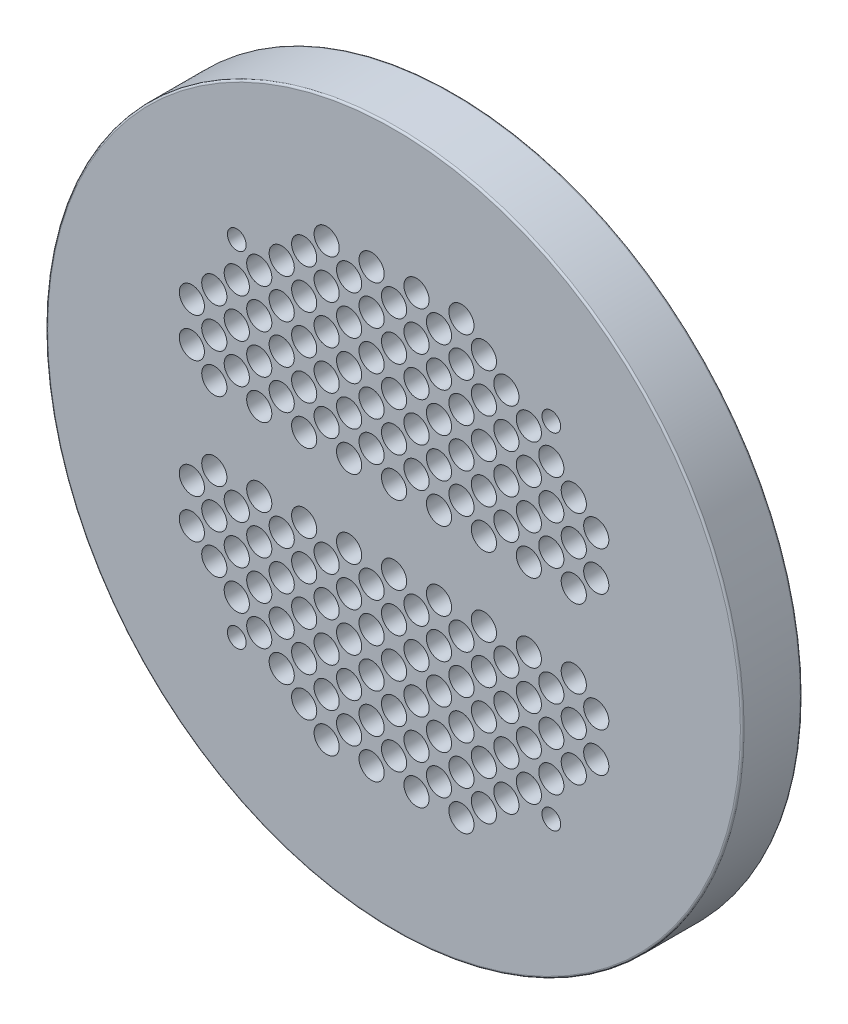
SolidWorks part; units mm, degrees
material "ASTM A105"
ref_plane "Front Plane" through (0, 0, 0) normal (0, 0, 1) x (1, 0, 0)
ref_plane "Top Plane" through (0, 0, 0) normal (0, 1, 0) x (1, 0, 0)
ref_plane "Right Plane" through (0, 0, 0) normal (1, 0, 0) x (0, 0, -1)
ref_axis "Axis1" through (0, 0, -1.27) along (0, 0, 1)
ref_plane "Hub End Plane" through (0, 0, 88.9) normal (0, 0, 1) x (1, 0, 0)
sketch "Sketch1" plane through (0, 0, 0) normal (0, 0, 1) x (1, 0, 0)
  line L0 (0, 314.325) -> (0, 0) construction
  line L1 (41.0276, 311.6359) -> (0, 0) construction
  circle A1 centre (0, 0) radius 295.275
  circle A2 centre (0, 0) radius 314.325 construction
  circle A3 centre (41.0276, 311.6359) radius 17.4625 construction
  dimension "FlangeOD" = 590.55
  dimension "BoltHoleDia" = 34.925
  dimension "BoltCircle" = 628.65
  dimension "HoleOffsetAngle" = 7.5
extrude "Boss-Extrude1" add sketch "Sketch1" along normal blind 50.8
sketch "Sketch7" plane through (0, 0, 0) normal (0, 0, 1) x (1, 0, 0)
  circle A0 centre (0, 0) radius 230.886
  dimension "ID" = 461.772
fillet "Fillet2" radius 1.5875 2 edges at (295.275, 0, 50.8) (295.275, 0, 0)
ref_plane "lug mating plane" through (0, 0, 25.4) normal (0, 0, 1) x (1, 0, 0)
sketch "Sketch11" plane through (0, 0, 0) normal (0, 0, 1) x (1, 0, 0)
  line L0 (-313.3441, 0) -> (312.1404, 0) construction
  line L1 (0, 318.8395) -> (0, -323.6955) construction
  circle A3 centre (0, 33.02) radius 10.668
  circle A15 centre (38.1, 33.02) radius 10.668
  circle A16 centre (76.2, 33.02) radius 10.668
  circle A17 centre (114.3, 33.02) radius 10.668
  circle A18 centre (152.4, 33.02) radius 10.668
  circle A20 centre (-38.1, 33.02) radius 10.668
  circle A21 centre (-76.2, 33.02) radius 10.668
  circle A22 centre (-114.3, 33.02) radius 10.668
  circle A23 centre (-152.4, 33.02) radius 10.668
  circle A88 centre (0, 66.3575) radius 10.668
  circle A89 centre (38.1, 66.3575) radius 10.668
  circle A90 centre (76.2, 66.3575) radius 10.668
  circle A91 centre (114.3, 66.3575) radius 10.668
  circle A93 centre (152.4, 66.3575) radius 10.668
  circle A95 centre (-38.1, 66.3575) radius 10.668
  circle A98 centre (-76.2, 66.3575) radius 10.668
  circle A146 centre (-114.3, 66.3575) radius 10.668
  circle A150 centre (-152.4, 66.3575) radius 10.668
  circle A152 centre (0, 99.695) radius 10.668
  circle A153 centre (38.1, 99.695) radius 10.668
  circle A154 centre (76.2, 99.695) radius 10.668
  circle A156 centre (114.3, 99.695) radius 10.668
  circle A158 centre (152.4, 99.695) radius 10.668
  circle A161 centre (-38.1, 99.695) radius 10.668
  circle A163 centre (-76.2, 99.695) radius 10.668
  circle A164 centre (-114.3, 99.695) radius 10.668
  circle A166 centre (-133.35, 146.05) radius 7.9375
  circle A172 centre (-152.4, 99.695) radius 10.668
  circle A174 centre (0, 133.0325) radius 10.668
  circle A175 centre (38.1, 133.0325) radius 10.668
  circle A176 centre (76.2, 133.0325) radius 10.668
  circle A177 centre (114.3, 133.0325) radius 10.668
  circle A180 centre (-38.1, 133.0325) radius 10.668
  circle A181 centre (-76.2, 133.0325) radius 10.668
  circle A182 centre (-114.3, 133.0325) radius 10.668
  circle A185 centre (0, 166.37) radius 10.668
  circle A186 centre (38.1, 166.37) radius 10.668
  circle A187 centre (76.2, 166.37) radius 10.668
  circle A191 centre (-38.1, 166.37) radius 10.668
  circle A192 centre (-76.2, 166.37) radius 10.668
  circle A207 centre (19.05, 49.8475) radius 10.668
  circle A208 centre (-19.05, 49.8475) radius 10.668
  circle A209 centre (-57.15, 49.8475) radius 10.668
  circle A210 centre (-95.25, 49.8475) radius 10.668
  circle A211 centre (-133.35, 49.8475) radius 10.668
  circle A212 centre (-171.45, 49.8475) radius 10.668
  circle A213 centre (57.15, 49.8475) radius 10.668
  circle A214 centre (95.25, 49.8475) radius 10.668
  circle A215 centre (133.35, 49.8475) radius 10.668
  circle A216 centre (171.45, 49.8475) radius 10.668
  circle A217 centre (19.05, 83.185) radius 10.668
  circle A218 centre (-19.05, 83.185) radius 10.668
  circle A219 centre (-57.15, 83.185) radius 10.668
  circle A220 centre (-95.25, 83.185) radius 10.668
  circle A221 centre (-133.35, 83.185) radius 10.668
  circle A222 centre (-171.45, 83.185) radius 10.668
  circle A223 centre (57.15, 83.185) radius 10.668
  circle A224 centre (95.25, 83.185) radius 10.668
  circle A225 centre (133.35, 83.185) radius 10.668
  circle A226 centre (171.45, 83.185) radius 10.668
  circle A227 centre (19.05, 116.5225) radius 10.668
  circle A228 centre (-19.05, 116.5225) radius 10.668
  circle A229 centre (-57.15, 116.5225) radius 10.668
  circle A230 centre (-95.25, 116.5225) radius 10.668
  circle A231 centre (-133.35, 116.5225) radius 10.668
  circle A233 centre (57.15, 116.5225) radius 10.668
  circle A234 centre (95.25, 116.5225) radius 10.668
  circle A235 centre (133.35, 116.5225) radius 10.668
  circle A237 centre (19.05, 149.86) radius 10.668
  circle A238 centre (-19.05, 149.86) radius 10.668
  circle A239 centre (-57.15, 149.86) radius 10.668
  circle A240 centre (-95.25, 149.86) radius 10.668
  circle A243 centre (57.15, 149.86) radius 10.668
  circle A244 centre (95.25, 149.86) radius 10.668
  circle A247 centre (19.05, 183.1975) radius 10.668
  circle A248 centre (-19.05, 183.1975) radius 10.668
  circle A249 centre (-57.15, 183.1975) radius 10.668
  circle A253 centre (57.15, 183.1975) radius 10.668
  circle A257 centre (-133.35, -146.05) radius 7.9375
  circle A258 centre (133.35, -146.05) radius 7.9375
  circle A262 centre (152.4, 199.7075) radius 10.668 [skipped]
  circle A263 centre (152.4, 166.37) radius 10.668 [skipped]
  circle A265 centre (114.3, 199.7075) radius 10.668 [skipped]
  circle A267 centre (-152.4, 199.7075) radius 10.668 [skipped]
  circle A268 centre (-114.3, 199.7075) radius 10.668 [skipped]
  circle A271 centre (-152.4, 166.37) radius 10.668 [skipped]
  circle A275 centre (152.4, 133.0325) radius 10.668 [skipped]
  circle A278 centre (114.3, 166.37) radius 10.668 [skipped]
  circle A280 centre (76.2, 199.7075) radius 10.668 [skipped]
  circle A281 centre (-114.3, 166.37) radius 10.668 [skipped]
  circle A283 centre (-76.2, 199.7075) radius 10.668 [skipped]
  circle A284 centre (-152.4, 133.0325) radius 10.668 [skipped]
  circle A288 centre (-190.5, 33.02) radius 10.668 [skipped]
  circle A290 centre (190.5, 33.02) radius 10.668 [skipped]
  circle A291 centre (38.1, 199.7075) radius 10.668 [skipped]
  circle A292 centre (0, 199.7075) radius 10.668 [skipped]
  circle A293 centre (-38.1, 199.7075) radius 10.668 [skipped]
  circle A294 centre (133.35, 146.05) radius 7.9375
  circle A299 centre (57.15, -183.1975) radius 10.668
  circle A300 centre (-57.15, -183.1975) radius 10.668
  circle A301 centre (-19.05, -183.1975) radius 10.668
  circle A302 centre (19.05, -183.1975) radius 10.668
  circle A303 centre (95.25, -149.86) radius 10.668
  circle A304 centre (57.15, -149.86) radius 10.668
  circle A305 centre (-95.25, -149.86) radius 10.668
  circle A306 centre (-57.15, -149.86) radius 10.668
  circle A307 centre (-19.05, -149.86) radius 10.668
  circle A308 centre (19.05, -149.86) radius 10.668
  circle A309 centre (133.35, -116.5225) radius 10.668
  circle A310 centre (95.25, -116.5225) radius 10.668
  circle A311 centre (57.15, -116.5225) radius 10.668
  circle A312 centre (-133.35, -116.5225) radius 10.668
  circle A313 centre (-95.25, -116.5225) radius 10.668
  circle A314 centre (-57.15, -116.5225) radius 10.668
  circle A315 centre (-19.05, -116.5225) radius 10.668
  circle A316 centre (19.05, -116.5225) radius 10.668
  circle A317 centre (171.45, -83.185) radius 10.668
  circle A318 centre (133.35, -83.185) radius 10.668
  circle A319 centre (95.25, -83.185) radius 10.668
  circle A320 centre (57.15, -83.185) radius 10.668
  circle A321 centre (-171.45, -83.185) radius 10.668
  circle A322 centre (-133.35, -83.185) radius 10.668
  circle A323 centre (-95.25, -83.185) radius 10.668
  circle A324 centre (-57.15, -83.185) radius 10.668
  circle A325 centre (-19.05, -83.185) radius 10.668
  circle A326 centre (19.05, -83.185) radius 10.668
  circle A327 centre (171.45, -49.8475) radius 10.668
  circle A328 centre (133.35, -49.8475) radius 10.668
  circle A329 centre (95.25, -49.8475) radius 10.668
  circle A330 centre (57.15, -49.8475) radius 10.668
  circle A331 centre (-171.45, -49.8475) radius 10.668
  circle A332 centre (-133.35, -49.8475) radius 10.668
  circle A333 centre (-95.25, -49.8475) radius 10.668
  circle A334 centre (-57.15, -49.8475) radius 10.668
  circle A335 centre (-19.05, -49.8475) radius 10.668
  circle A336 centre (19.05, -49.8475) radius 10.668
  circle A337 centre (-76.2, -166.37) radius 10.668
  circle A338 centre (-38.1, -166.37) radius 10.668
  circle A339 centre (76.2, -166.37) radius 10.668
  circle A340 centre (38.1, -166.37) radius 10.668
  circle A341 centre (0, -166.37) radius 10.668
  circle A342 centre (-114.3, -133.0325) radius 10.668
  circle A343 centre (-76.2, -133.0325) radius 10.668
  circle A344 centre (-38.1, -133.0325) radius 10.668
  circle A345 centre (114.3, -133.0325) radius 10.668
  circle A346 centre (76.2, -133.0325) radius 10.668
  circle A347 centre (38.1, -133.0325) radius 10.668
  circle A348 centre (0, -133.0325) radius 10.668
  circle A349 centre (-152.4, -99.695) radius 10.668
  circle A350 centre (-114.3, -99.695) radius 10.668
  circle A351 centre (-76.2, -99.695) radius 10.668
  circle A352 centre (-38.1, -99.695) radius 10.668
  circle A353 centre (152.4, -99.695) radius 10.668
  circle A354 centre (114.3, -99.695) radius 10.668
  circle A355 centre (76.2, -99.695) radius 10.668
  circle A356 centre (38.1, -99.695) radius 10.668
  circle A357 centre (0, -99.695) radius 10.668
  circle A358 centre (-152.4, -66.3575) radius 10.668
  circle A359 centre (-114.3, -66.3575) radius 10.668
  circle A360 centre (-76.2, -66.3575) radius 10.668
  circle A361 centre (-38.1, -66.3575) radius 10.668
  circle A362 centre (152.4, -66.3575) radius 10.668
  circle A363 centre (114.3, -66.3575) radius 10.668
  circle A364 centre (76.2, -66.3575) radius 10.668
  circle A365 centre (38.1, -66.3575) radius 10.668
  circle A366 centre (0, -66.3575) radius 10.668
  circle A367 centre (-152.4, -33.02) radius 10.668
  circle A368 centre (-114.3, -33.02) radius 10.668
  circle A369 centre (-76.2, -33.02) radius 10.668
  circle A370 centre (-38.1, -33.02) radius 10.668
  circle A371 centre (152.4, -33.02) radius 10.668
  circle A372 centre (114.3, -33.02) radius 10.668
  circle A373 centre (76.2, -33.02) radius 10.668
  circle A374 centre (38.1, -33.02) radius 10.668
  circle A375 centre (0, -33.02) radius 10.668
  dimension "D2" = 133.35
  dimension "D12" = 15.875
  dimension "D3" = 146.05
  dimension "D10" = 6
  dimension "D8" = 6
  dimension "D9" = 6
extrude "Cut-Extrude4" cut sketch "Sketch11" against normal through all and the other way through all
equation "\"D1@lug mating plane\"=\"FlangeThk@Boss-Extrude1\"/2"
